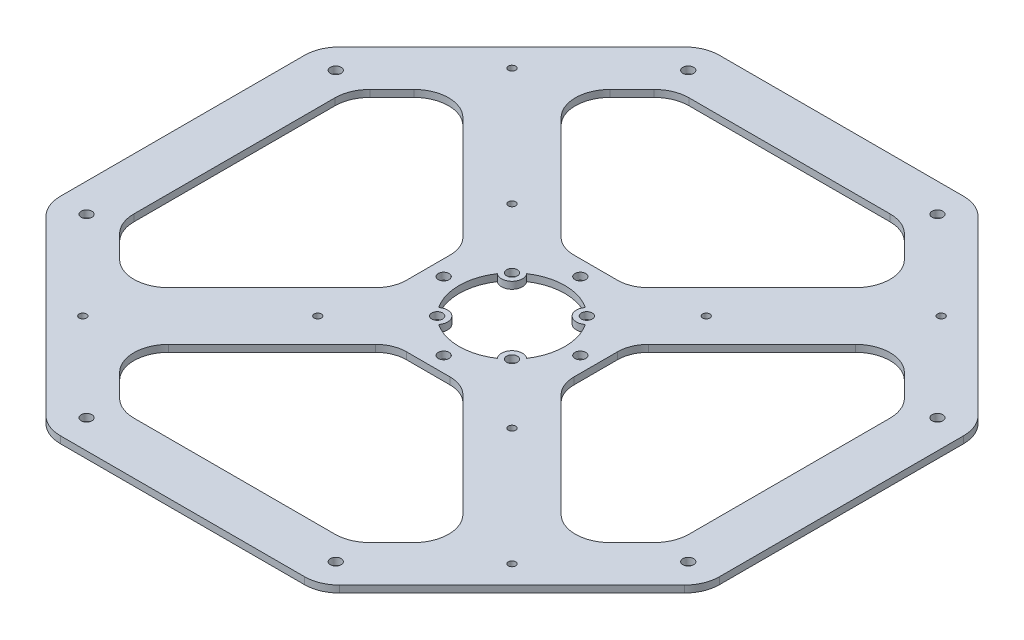
SolidWorks part; units mm, degrees
material "Hexcel AS4C (3000 Filaments)"
ref_plane "Front Plane" through (0, 0, 0) normal (0, 0, 1) x (1, 0, 0)
ref_plane "Top Plane" through (0, 0, 0) normal (0, 1, 0) x (1, 0, 0)
ref_plane "Right Plane" through (0, 0, 0) normal (1, 0, 0) x (0, 0, -1)
sketch "Sketch2" plane through (0, 0, 0) normal (0, 1, 0) x (1, 0, 0)
  line L0 (42.4264, 70.7107) -> (36.066, 77.0711)
  line L1 (92.0711, 42.2792) -> (42.2792, 92.0711)
  line L2 (35.2082, 95) -> (-35.2082, 95)
  line L3 (-42.2792, 92.0711) -> (-92.0711, 42.2792)
  line L4 (-95, 35.2082) -> (-95, -35.2082)
  line L5 (-92.0711, -42.2792) -> (-42.2792, -92.0711)
  line L6 (-35.2082, -95) -> (35.2082, -95)
  line L7 (42.2792, -92.0711) -> (92.0711, -42.2792)
  line L8 (95, -35.2082) -> (95, 35.2082)
  line L9 (28.9949, 80) -> (-28.9949, 80)
  line L10 (-70.7107, 42.4264) -> (-77.0711, 36.066)
  line L11 (-80, 28.9949) -> (-80, -28.9949)
  line L12 (-42.4264, -70.7107) -> (-36.066, -77.0711)
  line L13 (-28.9949, -80) -> (28.9949, -80)
  line L14 (70.7107, -42.4264) -> (77.0711, -36.066)
  line L15 (80, -28.9949) -> (80, 28.9949)
  line L68 (-80, 33.1371) -> (-80, -33.1371) construction
  line L69 (-80, -33.1371) -> (-33.1371, -80) construction
  line L70 (-33.1371, -80) -> (33.1371, -80) construction
  line L71 (33.1371, -80) -> (80, -33.1371) construction
  line L72 (80, -33.1371) -> (80, 33.1371) construction
  line L73 (80, 33.1371) -> (33.1371, 80) construction
  line L74 (33.1371, 80) -> (-33.1371, 80) construction
  line L75 (-33.1371, 80) -> (-80, 33.1371) construction
  line L76 (-95, 39.3503) -> (-95, -39.3503) construction
  line L77 (-95, -39.3503) -> (-39.3503, -95) construction
  line L78 (-39.3503, -95) -> (39.3503, -95) construction
  line L79 (39.3503, -95) -> (95, -39.3503) construction
  line L80 (95, -39.3503) -> (95, 39.3503) construction
  line L81 (95, 39.3503) -> (39.3503, 95) construction
  line L82 (39.3503, 95) -> (-39.3503, 95) construction
  line L83 (-39.3503, 95) -> (-95, 39.3503) construction
  line L84 (-26.7774, 12.6353) -> (-56.5685, 42.4264)
  line L93 (-12.6353, 26.7774) -> (-42.4264, 56.5685)
  line L94 (26.7774, 12.6353) -> (56.5685, 42.4264)
  line L95 (12.6353, 26.7774) -> (42.4264, 56.5685)
  line L96 (12.6353, -26.7774) -> (42.4264, -56.5685)
  line L97 (26.7774, -12.6353) -> (56.5685, -42.4264)
  line L98 (-26.7774, -12.6353) -> (-56.5685, -42.4264)
  line L99 (-12.6353, -26.7774) -> (-42.4264, -56.5685)
  line L100 (-6.2731, 24.1421) -> (6.2731, 24.1421)
  line L101 (24.1421, 6.2731) -> (24.1421, -6.2731)
  line L102 (6.2731, -24.1421) -> (-6.2731, -24.1421)
  line L103 (-24.1421, -6.2731) -> (-24.1421, 6.2731)
  line L104 (-36.066, 77.0711) -> (-42.4264, 70.7107)
  line L105 (77.0711, 36.066) -> (70.7107, 42.4264)
  line L106 (36.066, -77.0711) -> (42.4264, -70.7107)
  line L107 (-77.0711, -36.066) -> (-70.7107, -42.4264)
  line L108 (0, 15.25) -> (0, 24.1421)
  circle A0 centre (0, 0) radius 95 construction
  circle A1 centre (0, 0) radius 15.25
  arc A2 (-80, -28.9949) -> (-77.0711, -36.066) centre (-70, -28.9949) ccw
  arc A3 (-36.066, -77.0711) -> (-28.9949, -80) centre (-28.9949, -70) ccw
  arc A4 (28.9949, -80) -> (36.066, -77.0711) centre (28.9949, -70) ccw
  arc A5 (77.0711, -36.066) -> (80, -28.9949) centre (70, -28.9949) ccw
  arc A6 (77.0711, 36.066) -> (80, 28.9949) centre (70, 28.9949) cw
  arc A7 (36.066, 77.0711) -> (28.9949, 80) centre (28.9949, 70) ccw
  arc A8 (-28.9949, 80) -> (-36.066, 77.0711) centre (-28.9949, 70) ccw
  arc A9 (-77.0711, 36.066) -> (-80, 28.9949) centre (-70, 28.9949) ccw
  arc A10 (-95, -35.2082) -> (-92.0711, -42.2792) centre (-85, -35.2082) ccw
  arc A11 (-42.2792, -92.0711) -> (-35.2082, -95) centre (-35.2082, -85) ccw
  arc A12 (35.2082, -95) -> (42.2792, -92.0711) centre (35.2082, -85) ccw
  arc A13 (92.0711, -42.2792) -> (95, -35.2082) centre (85, -35.2082) ccw
  arc A14 (92.0711, 42.2792) -> (95, 35.2082) centre (85, 35.2082) cw
  arc A15 (42.2792, 92.0711) -> (35.2082, 95) centre (35.2082, 85) ccw
  arc A16 (-35.2082, 95) -> (-42.2792, 92.0711) centre (-35.2082, 85) ccw
  arc A17 (-92.0711, 42.2792) -> (-95, 35.2082) centre (-85, 35.2082) ccw
  arc A18 (-42.4264, -70.7107) -> (-42.4264, -56.5685) centre (-35.3553, -63.6396) cw
  arc A19 (70.7107, -42.4264) -> (56.5685, -42.4264) centre (63.6396, -35.3553) cw
  arc A20 (42.4264, 70.7107) -> (42.4264, 56.5685) centre (35.3553, 63.6396) cw
  arc A21 (-70.7107, 42.4264) -> (-56.5685, 42.4264) centre (-63.6396, 35.3553) cw
  arc A22 (-56.5685, -42.4264) -> (-70.7107, -42.4264) centre (-63.6396, -35.3553) cw
  arc A23 (42.4264, -56.5685) -> (42.4264, -70.7107) centre (35.3553, -63.6396) cw
  arc A24 (56.5685, 42.4264) -> (70.7107, 42.4264) centre (63.6396, 35.3553) cw
  arc A25 (-42.4264, 56.5685) -> (-42.4264, 70.7107) centre (-35.3553, 63.6396) cw
  arc A26 (-12.6353, -26.7774) -> (-6.2731, -24.1421) centre (-6.2731, -33.1396) cw
  arc A27 (12.6353, -26.7774) -> (6.2731, -24.1421) centre (6.2731, -33.1396) ccw
  arc A28 (26.7774, -12.6353) -> (24.1421, -6.2731) centre (33.1396, -6.2731) cw
  arc A29 (26.7774, 12.6353) -> (24.1421, 6.2731) centre (33.1396, 6.2731) ccw
  arc A30 (12.6353, 26.7774) -> (6.2731, 24.1421) centre (6.2731, 33.1396) cw
  arc A31 (-12.6353, 26.7774) -> (-6.2731, 24.1421) centre (-6.2731, 33.1396) ccw
  arc A32 (-26.7774, -12.6353) -> (-24.1421, -6.2731) centre (-33.1396, -6.2731) ccw
  arc A33 (-26.7774, 12.6353) -> (-24.1421, 6.2731) centre (-33.1396, 6.2731) cw
  circle A34 centre (-86.7388, 35.9284) radius 1.55
  circle A35 centre (-35.9284, 86.7388) radius 1.55
  circle A36 centre (35.9284, 86.7388) radius 1.55
  circle A37 centre (86.7388, 35.9284) radius 1.55
  circle A38 centre (86.7388, -35.9284) radius 1.55
  circle A39 centre (35.9284, -86.7388) radius 1.55
  circle A40 centre (-35.9284, -86.7388) radius 1.55
  circle A41 centre (-86.7388, -35.9284) radius 1.55
  circle A42 centre (10.7834, 10.7834) radius 1.55
  circle A43 centre (10.7834, -10.7834) radius 1.55
  circle A44 centre (-10.7834, -10.7834) radius 1.55
  circle A45 centre (-10.7834, 10.7834) radius 1.55
  circle A46 centre (10.7834, 10.7834) radius 3
  circle A47 centre (10.7834, -10.7834) radius 3
  circle A48 centre (-10.7834, -10.7834) radius 3
  circle A49 centre (-10.7834, 10.7834) radius 3
  circle A51 centre (0, 19.6961) radius 1.55
  circle A52 centre (19.6961, 0) radius 1.55
  circle A53 centre (0, -19.6961) radius 1.55
  circle A54 centre (-19.6961, 0) radius 1.55
  circle A55 centre (-28, 28) radius 1.05
  circle A56 centre (-61.8718, 61.8718) radius 1.05
  circle A57 centre (61.8718, 61.8718) radius 1.05
  circle A58 centre (28, 28) radius 1.05
  circle A59 centre (61.8718, -61.8718) radius 1.05
  circle A60 centre (28, -28) radius 1.05
  circle A61 centre (-61.8718, -61.8718) radius 1.05
  circle A62 centre (-28, -28) radius 1.05
  point P22 (0, 0)
  point P25 (0, 0)
  point P49 (0, 0)
  point P96 (0, 0)
  point P104 (-49.4975, 63.6396)
  point P105 (0, 0)
  point P142 (0, 0)
  point P150 (0, 0)
  point P159 (0, 0)
  point P169 (0, 0)
  point P187 (0, 0)
  dimension "D2" = 10
  dimension "D4" = 10
  dimension "D5" = 10
  dimension "D6" = 8.9974
  dimension "D7" = 4
  dimension "D9" = 4
  dimension "D3" = 4
  dimension "D1" = 15
  dimension "D8" = 1.45
extrude "Boss-Extrude1" add sketch "Sketch2" along normal blind 2 contours L3 A17 L4 A10 L5 A11 L6 A12 L7 A13 L8 A14 L1 A15 L2 A16 A49 A1 A46 A47 A48 A41 A40 A39 A38 A37 A36 A35 A34 A31 L93 A25 L104 A8 L9 A7 L0 A20 | A1 A48 A44 | A1 A48 A44 | A1 A49 A45 | A1 A49 A45 | A1 A46 A42 | A1 A46 A42 | A1 A47 A43 | A1 A47 A43 region at (11.7682, 0, -13.5373) region at (9.6735, 0, -9.6735) region at (-9.6735, 0, -9.6735) region at (-9.1034, 0, -12.3285) region at (-9.6735, 0, 9.6735) region at (-12.3285, 0, 9.1034) region at (13.4271, 0, 9.5324) region at (9.6735, 0, 9.6735) region at (91.7563, 0, -38.0067)
